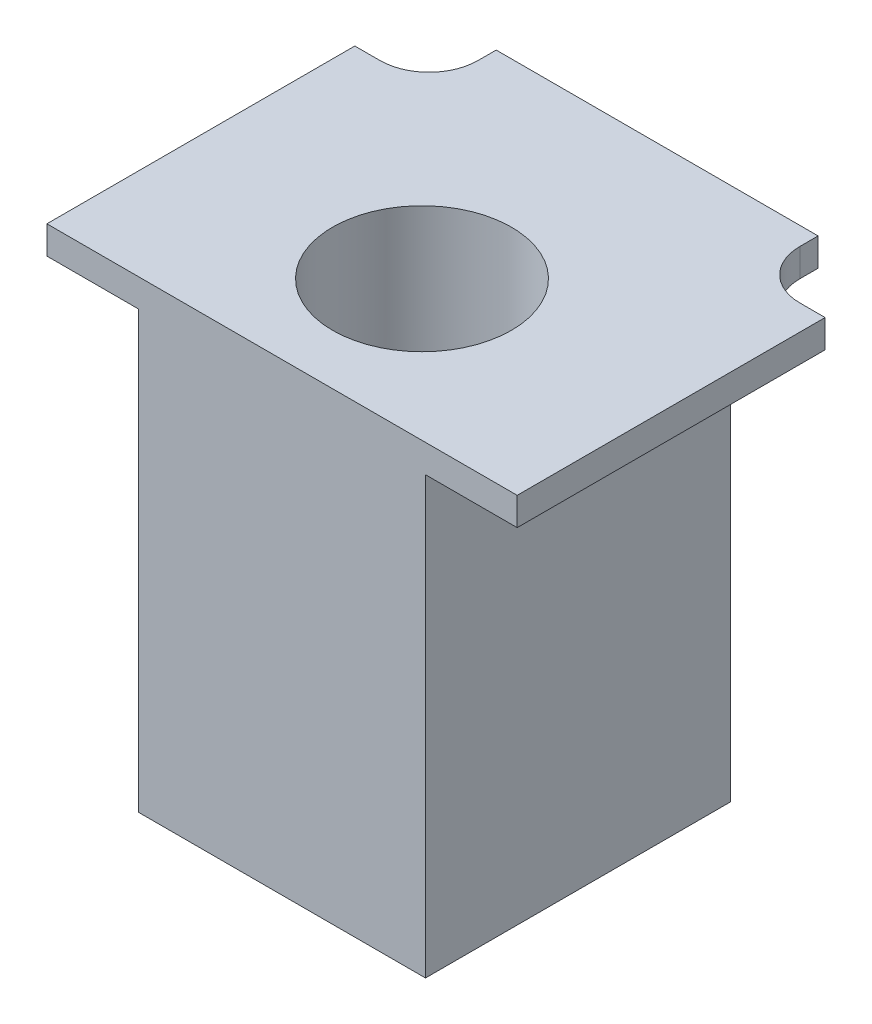
SolidWorks part; units mm, degrees
ref_plane "Front Plane" through (0, 0, 0) normal (0, 0, 1) x (1, 0, 0)
ref_plane "Top Plane" through (0, 0, 0) normal (0, 1, 0) x (1, 0, 0)
ref_plane "Right Plane" through (0, 0, 0) normal (1, 0, 0) x (0, 0, -1)
sketch "Sketch1" plane through (0, 0, 0) normal (0, 1, 0) x (1, 0, 0)
  line L1 (-5.125, 5.45) -> (5.125, 5.45)
  line L2 (-5.125, 5.45) -> (-5.125, -5.45)
  line L3 (-5.125, -5.45) -> (5.125, -5.45)
  line L4 (5.125, 5.45) -> (5.125, -5.45)
  line L5 (-5.125, 5.45) -> (5.125, -5.45) construction
  line L6 (-5.125, -5.45) -> (5.125, 5.45) construction
  point P0 (0, 0)
  dimension "D1" = 10.9
  dimension "D2" = 10.25
extrude "Boss-Extrude1" add sketch "Sketch1" along normal blind 1.5
sketch "Sketch2" plane through (0, 1.5, 0) normal (0, 1, 0) x (1, 0, 0)
  line L0 (-5.125, -5.45) -> (5.125, -5.45) construction
  line L5 (5.125, 5.45) -> (-5.125, 5.45) construction
  line L6 (-3.195, 3.75) -> (3.195, 3.75)
  line L7 (5.125, -5.45) -> (5.125, 5.45) construction
  line L8 (-5.125, 5.45) -> (-5.125, -5.45) construction
  line L11 (-3.195, 3.75) -> (-3.195, -4.65)
  line L12 (-3.195, -4.65) -> (3.195, -4.65)
  line L13 (3.195, 3.75) -> (3.195, -4.65)
  dimension "D1" = 1.7
  dimension "D2" = 0.8
  dimension "D3" = 1.93
  dimension "D4" = 1.93
extrude "Cut-Extrude1" cut sketch "Sketch2" against normal through all
sketch "Sketch3" plane through (0, 1.5, 0) normal (0, 1, 0) x (1, 0, 0)
  line L1 (-5.125, 5.45) -> (5.125, 5.45)
  line L2 (-5.125, 5.45) -> (-5.125, -5.45)
  line L3 (-5.125, -5.45) -> (5.125, -5.45)
  line L4 (5.125, 5.45) -> (5.125, -5.45)
  circle A0 centre (0, -0.45) radius 3.195
  dimension "D1" = 6.39
  dimension "D2" = 5.9
extrude "Boss-Extrude2" add sketch "Sketch3" along normal blind 15.07
sketch "Sketch5" plane through (0, 16.57, 0) normal (0, 1, 0) x (1, 0, 0)
  line L5 (-5.125, -5.45) -> (5.125, -5.45) construction
  line L44 (-10, 9.55) -> (10, 9.55) construction
  line L49 (-10, 9.55) -> (-10, -5.45) construction
  line L50 (-10, -5.45) -> (10, -5.45) construction
  line L51 (10, 9.55) -> (10, -5.45) construction
  line L53 (0, -0.45) -> (-4, -0.45) construction
  line L54 (-9.12, 8.67) -> (9.12, 8.67) construction
  line L55 (-9.12, 8.67) -> (-9.12, -5.45) construction
  line L56 (-9.12, -5.45) -> (9.12, -5.45) construction
  line L57 (9.12, 8.67) -> (9.12, -5.45) construction
  line L58 (-8.4, 7.95) -> (8.4, 7.95) construction
  line L59 (-8.4, 7.95) -> (-8.4, -5.45) construction
  line L60 (-8.4, -5.45) -> (8.4, -5.45) construction
  line L61 (8.4, 7.95) -> (8.4, -5.45) construction
  line L62 (0, -0.45) -> (0, -4.45) construction
  line L63 (-5.75, 7.3) -> (-5.75, 7.95)
  line L64 (-7.5, 5.55) -> (-8.4, 5.55)
  line L65 (-8.4, 7.95) -> (-5.75, 7.95)
  line L66 (-8.4, 5.55) -> (-8.4, 7.95)
  line L67 (7.5, 5.55) -> (8.4, 5.55)
  line L68 (8.4, 5.55) -> (8.4, 7.95)
  line L69 (5.75, 7.3) -> (5.75, 7.95)
  line L70 (5.75, 7.95) -> (8.4, 7.95)
  line L71 (-8.4, 5.55) -> (-8.4, -5.45)
  line L72 (-8.4, -5.45) -> (8.4, -5.45)
  line L73 (8.4, -5.45) -> (8.4, 5.55)
  line L74 (-5.75, 7.95) -> (5.75, 7.95)
  circle A0 centre (-7.5, 7.3) radius 1.75 construction
  circle A1 centre (7.5, 7.3) radius 1.75 construction
  arc A4 (5.75, 7.3) -> (7.5, 5.55) centre (7.5, 7.3) ccw
  arc A5 (-7.5, 5.55) -> (-5.75, 7.3) centre (-7.5, 7.3) ccw
  point P10 (0, -0.45)
  line M9 (-5.125, 5.45) -> (-5.125, -5.45)
  line M11 (5.125, -5.45) -> (5.125, 5.45)
  line M12 (5.125, 5.45) -> (-5.125, 5.45)
  circle M13 centre (0, -0.45) radius 3.195
  dimension "D4" = 0.88
  dimension "D10" = 3.5
  dimension "D3" = 10
  dimension "D5" = 0.88
  dimension "D7" = 1.6
  dimension "D8" = 1.6
  dimension "D13" = 10
  dimension "D2" = 10
  dimension "D6" = 0.88
  dimension "D9" = 1.6
  dimension "D11" = 2.25
  dimension "D12" = 2.5
extrude "Boss-Extrude3" add sketch "Sketch5" against normal blind 1 contours M12 M13 M11 M9 region at (-5.5351, 16.57, -7.625)
